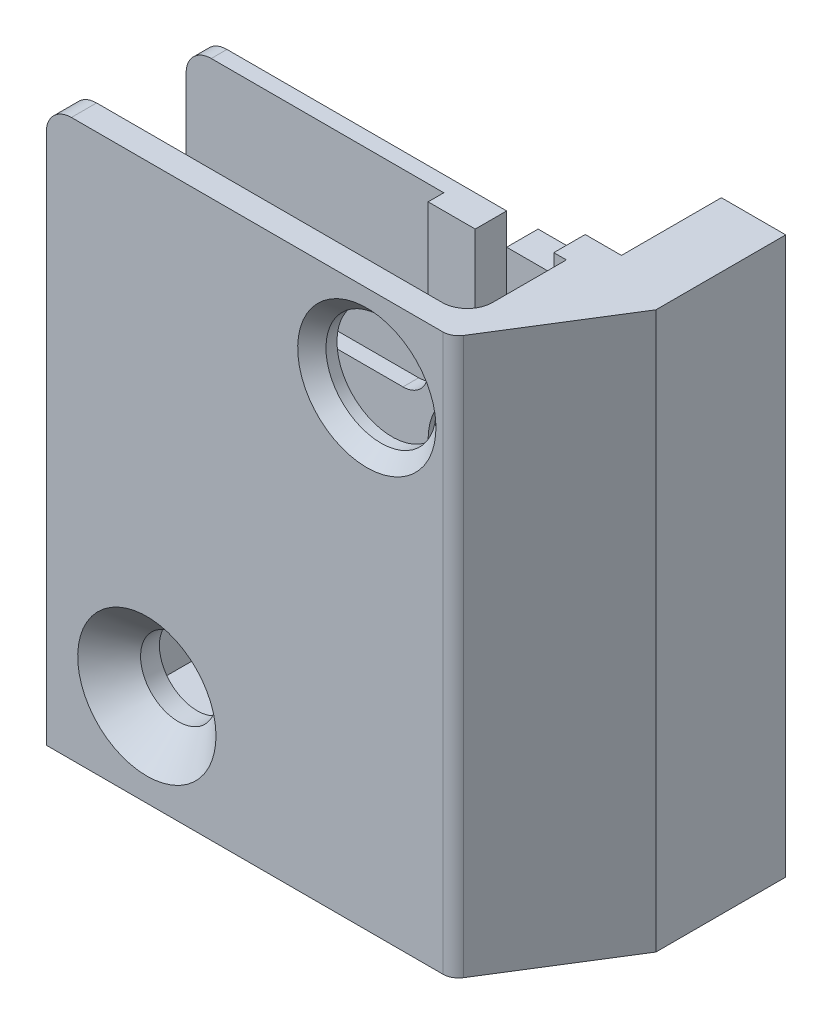
SolidWorks part; units mm, degrees
note: The reader was unsure of these and kept them because the rebuilt part matched: shared geometry of "Sketch3<2>".
ref_plane "Front Plane" through (0, 0, 0) normal (0, 0, 1) x (1, 0, 0)
ref_plane "Top Plane" through (0, 0, 0) normal (0, 1, 0) x (1, 0, 0)
ref_plane "Right Plane" through (0, 0, 0) normal (1, 0, 0) x (0, 0, -1)
sketch "Sketch2" plane through (0, 0, 0) normal (1, 0, 0) x (0, 0, -1)
  line L0 (0, 0) -> (-4.95, 0)
  line L1 (-4.95, 0) -> (-4.95, 17.7)
  line L2 (-4.95, 17.7) -> (-4.15, 17.7)
  line L3 (-4.15, 17.7) -> (-4.15, 0.8)
  line L4 (-4.15, 0.8) -> (-1, 0.8)
  line L5 (-1, 0.8) -> (-1, 17.7)
  line L6 (-1, 17.7) -> (0, 17.7)
  line L7 (0, 17.7) -> (0, 0)
  dimension "D2" = 17.7
  dimension "D3" = 3.15
  dimension "D4" = 0.8
  dimension "D5" = 1
  dimension "D1" = 0.8
extrude "Boss-Extrude1" add sketch "Sketch2" along normal blind 15.4
sketch "Sketch3" plane through (0, 0, 4.95) normal (0, 0, 1) x (1, 0, 0)
  line L0 (15.4, 0) -> (0, 0) construction
  line L1 (0, 17.7) -> (7.5, 17.7)
  line L2 (0, 17.7) -> (0, 6.2)
  line L3 (0, 6.2) -> (7.5, 6.2)
  line L4 (7.5, 17.7) -> (7.5, 6.2)
  line L7 (15.4, 17.7) -> (15.4, 0) construction
  circle A0 centre (3.2, 2.95) radius 1.2 construction
  circle A1 centre (10.2, 14.95) radius 1.2 construction
  dimension "D3" = 2.4
  dimension "D8" = 2.4
  dimension "D1" = 2.95
  dimension "D4" = 11.5
  dimension "D5" = 7.5
  dimension "D7" = 5.2
  dimension "D6" = 12
  dimension "D2" = 7
extrude "Cut-Extrude2" cut sketch "Sketch3" against normal up to next
sketch "Sketch4" plane through (0, 0, 4.95) normal (0, 0, 1) x (1, 0, 0)
  line L0 (0, 6.2) -> (7.5, 6.2) construction
  line L1 (0, 0) -> (0.8, 0)
  line L2 (0, 0) -> (0, 6.2)
  line L3 (0, 6.2) -> (0.8, 6.2)
  line L4 (0.8, 0) -> (0.8, 6.2)
  line L5 (15.4, 17.7) -> (7.5, 17.7) construction
  line L6 (15.4, 0) -> (12.6, 0)
  line L7 (15.4, 0) -> (15.4, 17.7)
  line L8 (15.4, 17.7) -> (12.6, 17.7)
  line L9 (12.6, 0) -> (12.6, 17.7)
  dimension "D1" = 0.8
  dimension "D2" = 2.8
extrude "Boss-Extrude3" add sketch "Sketch4" against normal through all
sketch "Sketch10" plane through (0, 17.7, 0) normal (0, 1, 0) x (1, 0, 0)
  line L1 (12.6, -1) -> (0.8, -1) construction
  line L3 (12.2, -1) -> (12.2, 0)
  line L4 (15.4, 0) -> (0, 0) construction
  line L5 (12.2, 0) -> (8.2, 0)
  line L6 (8.2, 0) -> (8.2, -1)
  line L9 (12.6, -1) -> (0, -1) construction
  line L10 (8.2, -1) -> (12.2, -1)
  line L11 (15.4, 0) -> (0, 0) construction
  point P0 (12.6, 0)
  point P1 (10.2, 0)
  dimension "D1" = 4
  dimension "D2" = 2.4
extrude "Cut-Extrude4" cut sketch "Sketch10" against normal blind 16.3
sketch "Sketch6" plane through (0, 0, 4.15) normal (0, 0, -1) x (-1, 0, 0)
  line L0 (-15.4, 0) -> (-15.4, 17.7) construction
  line L1 (-14.6, 17.6) -> (-8.35, 17.6) construction
  line L2 (-14.6, 17.6) -> (-14.6, 13.1) construction
  line L3 (-14.6, 13.1) -> (-10.2, 13.1) construction
  line L4 (-8.35, 17.6) -> (-8.35, 14.95) construction
  line L5 (-0.8, 0.8) -> (-5.05, 0.8)
  line L6 (-0.8, 0.8) -> (-0.8, 4.8)
  line L7 (-0.8, 4.8) -> (-3.2, 4.8)
  line L8 (-5.05, 0.8) -> (-5.05, 2.95)
  arc A0 (-10.2, 13.1) -> (-8.35, 14.95) centre (-10.2, 14.95) ccw construction
  arc A1 (-3.2, 4.8) -> (-5.05, 2.95) centre (-3.2, 2.95) ccw
  dimension "D2" = 1.85
  dimension "D1" = 1.85
  dimension "D3" = 0.8
extrude "Boss-Extrude4" add sketch "Sketch6" along normal blind 0.8
hole_wizard "CSK for M2 Flat Head Machine Screw3" positions "3DSketch3" profile "Sketch8" countersink size "M2" standard "ANSI Metric" end condition through all
sketch3d "3DSketch3"
  point P0 (10.2, 14.95, 4.95)
  point P3 (3.2, 2.95, 4.95)
sketch "Sketch8" plane through (10.2, 14.95, 4.95) normal (1, 0, 0) x (0, -1, 0)
  line L0 (0, 0) -> (0, 4.95)
  line L1 (0, 4.95) -> (1.2, 4.95)
  line L2 (1.2, 4.95) -> (1.2, 1)
  line L3 (1.2, 1) -> (2.2, 0)
  line L5 (2.2, 0) -> (0, 0)
  line L6 (-1.2, 1) -> (-2.2, 0) construction
  line L11 (0, -6.35) -> (0, 107.95) construction
  dimension "Thru Hole Dia." = 2.4
  dimension "Thru Hole Depth" = 4.95
  dimension "Near C'Sink Dia." = 4.4
  dimension "Near C'Sink Angle" = 90
other "Move Face1" face at (4.1, 17.7, 0.5) parameters "D1"=0.6
extrude "Boss-Extrude6" add sketch "Sketch3<2>" against normal up to surface (0.8 mm away) up to face at (10.2, 13.55, 4.15)
sketch "Sketch3<2>" plane through (0, 0, 4.95) normal (0, 0, 1) x (1, 0, 0) same geometry as "Sketch3"
chamfer "Chamfer1" distance 2.5 distance2 4 1 edges at (15.4, 8.85, 4.95)
sketch "Sketch12" plane through (0, 17.7, 0) normal (0, 1, 0) x (1, 0, 0)
  line L0 (16.5389, 2.7148) -> (17.5509, -0.4) construction
  line L1 (13.3525, 0) -> (15.4, 0)
  line L2 (13.3525, 0) -> (13.3525, 3.18)
  line L3 (13.3525, 3.18) -> (15.4, 3.18)
  line L4 (15.4, 0) -> (15.4, 3.18)
  line L5 (17.5509, -0.4) -> (16.9803, -0.5854) construction
  line L7 (15.9205, 2.2148) -> (16.0705, 2.2148) construction
  line L8 (16.0705, 2.2148) -> (16.9803, -0.5854) construction
  dimension "D1" = 3.18
  dimension "D2" = 0.15
  dimension "D3" = 0.6
  dimension "D4" = 0.5
  dimension "D5" = 18
  dimension "D6" = 0.4
  dimension "D7" = 0.7525
extrude "Boss-Extrude5" add sketch "Sketch12" against normal blind 17.7
sketch "Sketch11" plane through (0, 0, 4.15) normal (0, 0, -1) x (-1, 0, 0)
  circle A0 centre (-10.2, 14.95) radius 1.75
  dimension "D1" = 3.5
extrude "Cut-Extrude5" cut sketch "Sketch11" against normal through all
sketch "Sketch14" plane through (0, 0, 0) normal (0, 0, -1) x (-1, 0, 0)
  line L0 (-12.6, 17.7) -> (0, 17.7) construction
  line L1 (-12.2, 1.4) -> (-12.2, 17.7) construction
  line L2 (-10.2, 1.4) -> (-10.2, 10.55) construction
  line L3 (-12.2, 1.4) -> (-8.2, 1.4) construction
  line L4 (-12.2, 10.55) -> (-8.2, 10.55)
  line L5 (-12.2, 10.55) -> (-12.2, 17.1)
  line L6 (-12.2, 17.1) -> (-8.2, 17.1)
  line L7 (-8.2, 10.55) -> (-8.2, 17.1)
  line L9 (-10.7, 17.1) -> (-9.7, 17.1)
  line L10 (-10.7, 17.1) -> (-10.7, 10.55)
  line L11 (-10.7, 10.55) -> (-9.7, 10.55)
  line L12 (-9.7, 17.1) -> (-9.7, 10.55)
  circle A0 centre (-10.2, 10.55) radius 1.5
  circle A1 centre (-10.2, 10.55) radius 2
  point P17 (-10.2, 10.55)
  line M13 (-8.2, 17.1) -> (-8.2, 1.4)
  line M15 (-12.2, 1.4) -> (-12.2, 17.7)
  dimension "D1" = 7.15
  dimension "D2" = 3
  dimension "D3" = 4
  dimension "D4" = 1
extrude "Boss-Extrude7" add sketch "Sketch14" against normal up to surface (1 mm away) contours A1 L10 L6 M15 | A1 L6 L12 M13 up to face at (3.2, 4.15, 1)
sketch "Sketch16" plane through (0, 0, 1) normal (0, 0, 1) x (1, 0, 0)
  line L1 (0, 17.1) -> (8.2, 17.1)
  line L2 (0, 17.1) -> (0, 11.6)
  line L3 (0, 11.6) -> (8.2, 11.6)
  line L4 (8.2, 17.1) -> (8.2, 11.6)
  line L5 (9.7, 12.4865) -> (9.7, 17.1) construction
  dimension "D1" = 5.5
  dimension "D2" = 1.5
extrude "Cut-Extrude6" cut sketch "Sketch16" against normal blind 0.5
fillet "Fillet5" radius 0.5 1 edges at (12.9, 8.85, 4.95)
fillet "Fillet6" radius 0.8 6 edges at (0.4, 6.2, 4.15) (0, 17.7, 4.55) (12.6, 9.25, 4.15) (0.8, 5.5, 4.15) (8.2, 11.6, 0.75) (0.4, 6.2, 1)
delete or keep bodies "Body-Delete/Keep 1" [suppressed] type delete bodies bodies 112
mirror "Mirror1" [suppressed]
delete or keep bodies "Body-Delete/Keep 2" [suppressed] type delete bodies bodies 114
equation "\"BoardLength\"= 11'mech 305"
equation "\"BoardHeight\"= 16'is"
equation "\"BoardThickness\"= 3'pain"
equation "\"ScrewHoleDiameter\"= 2.4'and"
equation "\"PrintThickness\"= 0.8'suffering"
equation "\"D2@Sketch2\"=\"BoardHeight\"+\"PrintThickness\"+\"Tolerance\"+0.75"
equation "\"D3@Sketch2\"=\"BoardThickness\"+\"Tolerance\""
equation "\"D4@Sketch2\"=\"PrintThickness\""
equation "\"D1@Boss-Extrude1\"=\"BoardLength\"+\"PrintThickness\"*2+\"Tolerance\"*2+1.5+1"
equation "\"D3@Sketch3\"=\"ScrewHoleDiameter\""
equation "\"D1@Sketch3\"=\"PrintThickness\"+2+\"Tolerance\""
equation "\"D1@Sketch4\"=\"PrintThickness\""
equation "\"D7@Sketch3\"=\"PrintThickness\"+3.25+\"Tolerance\"+1"
equation "\"D8@Sketch3\"=\"ScrewHoleDiameter\""
equation "\"MetalRingOuterDiameter\"= 3.7'drop it"
equation "\"D2@Sketch6\"=\"MetalRingOuterDiameter\"/2"
equation "\"DribblerPlateThickness\"= 3.18"
equation "\"D1@Sketch6\"=\"MetalRingOuterDiameter\"/2"
equation "\"Tolerance\"= 0.15"
equation "\"D2@Sketch4\"=\"PrintThickness\"+1+1"
equation "\"D1@Sketch2\"=\"PrintThickness\""
equation "\"D1@Cut-Extrude4\"=\"BoardHeight\"+\"Tolerance\"*2"
